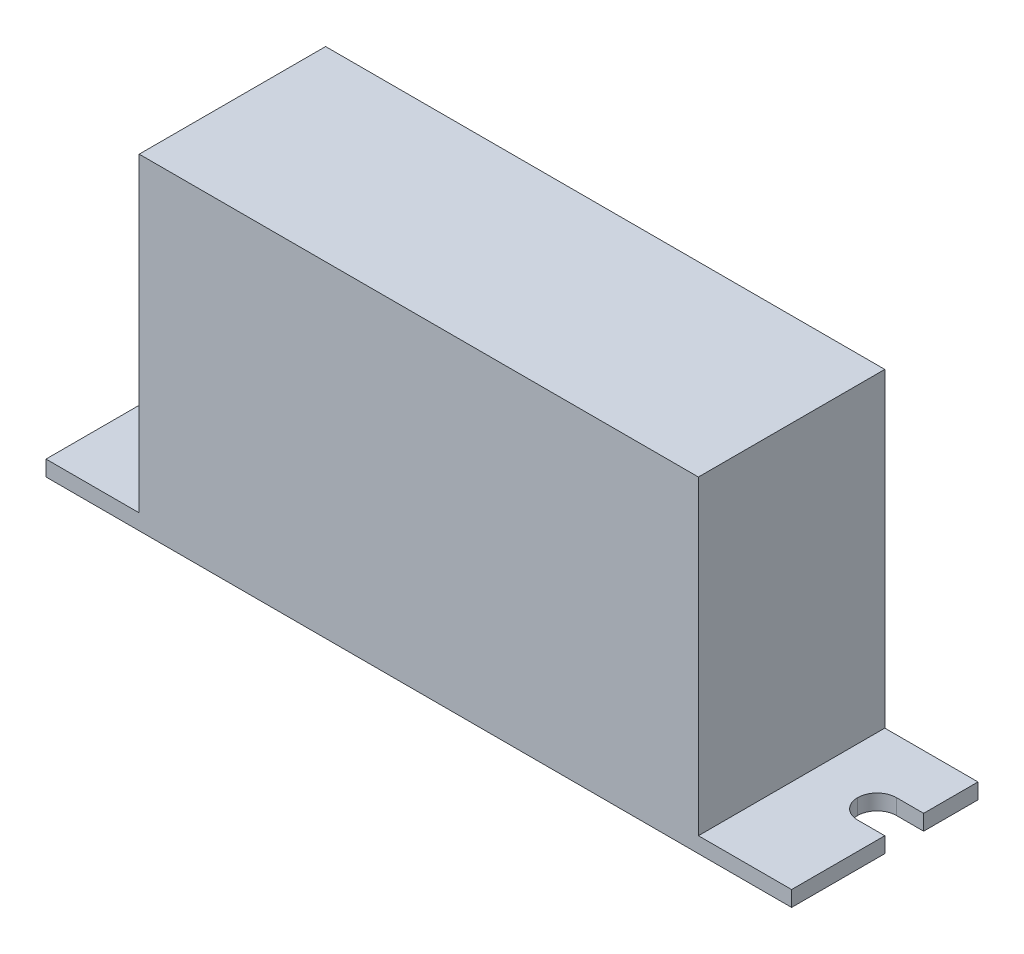
SolidWorks part; units mm, degrees
material "Plain Carbon Steel"
ref_plane "Front Plane" through (0, 0, 0) normal (0, 0, 1) x (1, 0, 0)
ref_plane "Top Plane" through (0, 0, 0) normal (0, 1, 0) x (1, 0, 0)
ref_plane "Right Plane" through (0, 0, 0) normal (1, 0, 0) x (0, 0, -1)
sketch "Sketch1" plane through (0, 0, 0) normal (0, 0, 1) x (1, 0, 0)
  line L0 (0, 0) -> (96, 0)
  line L1 (96, 0) -> (96, 2)
  line L2 (96, 2) -> (84, 2)
  line L3 (84, 2) -> (84, 42)
  line L4 (84, 42) -> (12, 42)
  line L5 (12, 42) -> (12, 2)
  line L6 (12, 2) -> (0, 2)
  line L7 (0, 2) -> (0, 0)
  dimension "D1" = 96
  dimension "D2" = 2
  dimension "D3" = 72
  dimension "D4" = 40
extrude "body" add sketch "Sketch1" along normal blind 24
sketch "Sketch2" plane through (0, 2, 0) normal (0, 1, 0) x (1, 0, 0)
  line L0 (0, -24) -> (0, 0) construction
  line L1 (0, -12) -> (6, -12)
  line L2 (0, -12) -> (0, -7)
  line L3 (0, -7) -> (6, -7)
  line L4 (6, -12) -> (6, -7)
  line L5 (96, -24) -> (96, 0) construction
  line L6 (96, -12) -> (90, -12)
  line L7 (96, -12) -> (96, -7)
  line L8 (96, -7) -> (90, -7)
  line L9 (90, -12) -> (90, -7)
  line L10 (12, -24) -> (0, -24) construction
  dimension "D1" = 5
  dimension "D2" = 12
  dimension "D3" = 6
extrude "fixation_cutout" cut sketch "Sketch2" against normal through all
fillet "fixation_cutout_rounds" radius 2.5 4 edges at (90, 1, 12) (90, 1, 7) (6, 1, 12) (6, 1, 7)
